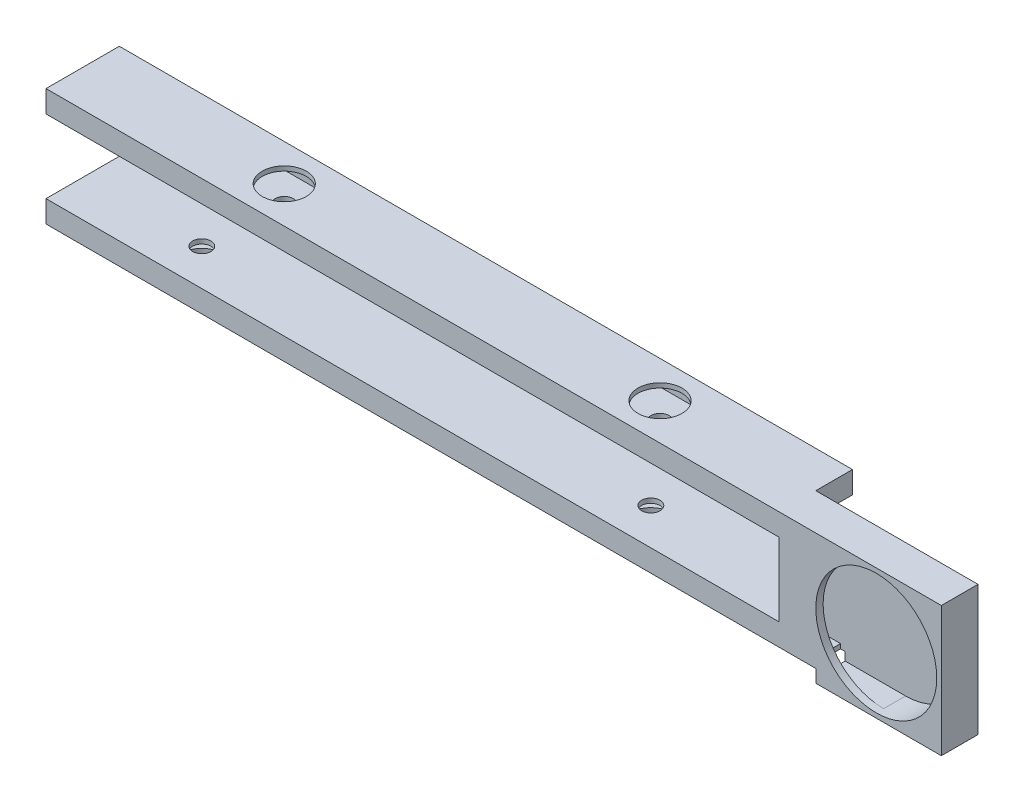
SolidWorks part; units mm, degrees
note: The reader was unsure of these and kept them because the rebuilt part matched: shared geometry of "Sketch1<12>", "Sketch1<14>", "Sketch1<20>", "Sketch1<21>", "Sketch2<3>", "Sketch3<3>".
material "Custom Plastic"
ref_plane "Front Plane" through (0, 0, 0) normal (0, 0, 1) x (1, 0, 0)
ref_plane "Top Plane" through (0, 0, 0) normal (0, 1, 0) x (1, 0, 0)
ref_plane "Right Plane" through (0, 0, 0) normal (1, 0, 0) x (0, 0, -1)
sketch "Sketch1" plane through (0, 0, 0) normal (0, 0, 1) x (1, 0, 0)
  line L0 (200, 6) -> (200, 26)
  line L1 (0, 0) -> (200, 0)
  line L2 (0, 0) -> (0, 6)
  line L3 (0, 6) -> (200, 6)
  line L4 (200, 0) -> (200, 6)
  line L5 (200, 0) -> (210, 0)
  line L6 (200, 26) -> (0, 26)
  line L7 (200, 26) -> (200, 32)
  line L8 (200, 32) -> (0, 32)
  line L9 (0, 26) -> (0, 32)
  line L10 (210, 0) -> (210, 32)
  line L11 (210, 32) -> (200, 32)
  line L12 (1.25, 1.25) -> (208.75, 1.25)
  line L13 (208.75, 1.25) -> (208.75, 30.75)
  line L14 (208.75, 30.75) -> (1.25, 30.75)
  line L15 (1.25, 30.75) -> (1.25, 27.25)
  line L16 (1.25, 27.25) -> (201.25, 27.25)
  line L17 (201.25, 27.25) -> (201.25, 4.75)
  line L18 (201.25, 4.75) -> (1.25, 4.75)
  line L19 (1.25, 4.75) -> (1.25, 1.25)
  line L20 (1.25, 3) -> (0, 3) construction
  line L21 (1.25, 29) -> (0, 29) construction
  line L22 (208.75, 16) -> (210, 16) construction
  line L23 (200, 16) -> (201.25, 16) construction
  line L24 (1.25, 1.25) -> (1.25, 0) construction
  line L25 (210, 32) -> (244.25, 32)
  line L26 (244.25, 32) -> (244.25, -3.5)
  line L27 (244.25, -3.5) -> (210, -3.5)
  line L28 (210, -3.5) -> (210, 0)
  line L29 (208.75, 30.75) -> (243, 30.75) construction
  line L30 (243, 30.75) -> (243, -2.25) construction
  line L31 (243, -2.25) -> (208.75, -2.25) construction
  line L32 (208.75, -2.25) -> (208.75, 1.25)
  line L33 (243, 14.25) -> (244.25, 14.25) construction
  line L34 (243, 30.75) -> (210, -2.25) construction
  line L35 (208.75, -2.25) -> (226.5, -2.25)
  line L36 (226.5, 30.75) -> (208.75, 30.75)
  line L37 (201.25, 4.75) -> (201.25, 1.25)
  line L38 (201.25, 27.25) -> (201.25, 30.75)
  line L39 (200, 30.75) -> (200, 32)
  line L40 (200, 26) -> (200, 27.25)
  line L41 (198.75, 30.75) -> (198.75, 27.25)
  line L42 (198.75, 4.75) -> (198.75, 1.25)
  line L43 (201.25, 29) -> (200, 29) construction
  line L44 (200, 29) -> (198.75, 29) construction
  circle A0 centre (226.5, 14.25) radius 16.5
  dimension "D6" = 33
  dimension "D1" = 200
  dimension "D2" = 6
  dimension "D3" = 20
  dimension "D4" = 10
  dimension "D5" = 1.25
extrude "Boss-Extrude11" add sketch "Sketch1" against normal blind 10 contours A0 L35 L10 L27 L26 L25 L36 | L36 L10 L11 L7 L14 | L16 L15 L14 L7 L8 L9 L6 | L18 L17 L16 L7 L0 L4 | L35 L13 L12 L4 L5 L10 | L19 L18 L4 L3 L2 L1 L12
extrude "Boss-Extrude12" add sketch "Sketch1<12>" against normal blind 2
sketch "Sketch1<12>" plane through (0, 0, 0) normal (0, 0, 1) x (1, 0, 0) same geometry as "Sketch1"
extrude "Boss-Extrude15" add sketch "Sketch1<14>" along normal blind 2 from offset 10 contours A0 | A0 L35 L10 L27 L26 L25 L36 | A0 L36 L10 | A0 L10 L35 | L10 L36 L13 L35 | L38 L17 L37 L12 L13 L14 | L16 L38 L14 L7 | L37 L18 L4 L12 | L18 L42 L12 L4 | L14 L41 L16 L7 offset against normal yes
sketch "Sketch1<14>" plane through (0, 0, 0) normal (0, 0, 1) x (1, 0, 0) same geometry as "Sketch1"
extrude "Boss-Extrude19" add sketch "Sketch1<20>" against normal blind 10 from offset 10 contours L16 L15 L14 L7 L8 L9 L6 | L14 L41 L16 L7 | L18 L42 L12 L4 | L19 L18 L4 L3 L2 L1 L12 offset against normal yes
sketch "Sketch1<20>" plane through (0, 0, 0) normal (0, 0, 1) x (1, 0, 0) same geometry as "Sketch1"
extrude "Boss-Extrude20" add sketch "Sketch1<21>" along normal blind 2 from offset 20 contours L42 L18 L19 L12 | L41 L14 L15 L16 offset against normal yes
sketch "Sketch1<21>" plane through (0, 0, 0) normal (0, 0, 1) x (1, 0, 0) same geometry as "Sketch1"
sketch "Sketch2" plane through (0, 0, 0) normal (0, -1, 0) x (1, 0, 0)
  line L0 (32.5, 0) -> (32.5, -20) construction
  line L1 (0, 0) -> (210, 0) construction
  line L2 (0, -20) -> (200, -20) construction
  line L3 (155, 0) -> (155, -20) construction
  circle A0 centre (32.5, -10) radius 2.5
  circle A1 centre (155, -10) radius 2.5
  circle A2 centre (32.5, -10) radius 6
  circle A3 centre (155, -10) radius 6
  dimension "D1" = 5
  dimension "D2" = 12
  dimension "D3" = 32.5
  dimension "D4" = 122.5
extrude "Cut-Extrude1" cut sketch "Sketch2" against normal up to surface (6 mm away) contours A0 | A1 up to face at (120, 6, -10)
extrude "Cut-Extrude2" cut sketch "Sketch2<3>" against normal up to surface (4.75 mm away) contours A3 A1 | A2 A0 up to face at (152.5, 4.75, -10)
sketch "Sketch2<3>" plane through (0, 0, 0) normal (0, -1, 0) x (1, 0, 0) same geometry as "Sketch2"
sketch "Sketch3" plane through (0, 32, 0) normal (0, 1, 0) x (1, 0, 0)
  line L0 (157.5, 0) -> (157.5, 20) construction
  line L1 (0, 0) -> (244.25, 0) construction
  line L2 (200, 20) -> (0, 20) construction
  line L3 (55, 0) -> (55, 20) construction
  circle A0 centre (157.5, 10) radius 2.5
  circle A1 centre (157.5, 10) radius 6
  circle A2 centre (55, 10) radius 2.5
  circle A3 centre (55, 10) radius 6
  dimension "D2" = 5
  dimension "D3" = 12
  dimension "D1" = 55
  dimension "D4" = 102.5
extrude "Cut-Extrude3" cut sketch "Sketch3" against normal up to surface (6 mm away) contours A0 | A2 up to face at (120, 26, -10)
extrude "Cut-Extrude4" cut sketch "Sketch3<3>" against normal up to surface (4.75 mm away) contours A1 A0 | A3 A2 up to face at (57.5, 27.25, -10)
sketch "Sketch3<3>" plane through (0, 32, 0) normal (0, 1, 0) x (1, 0, 0) same geometry as "Sketch3"
